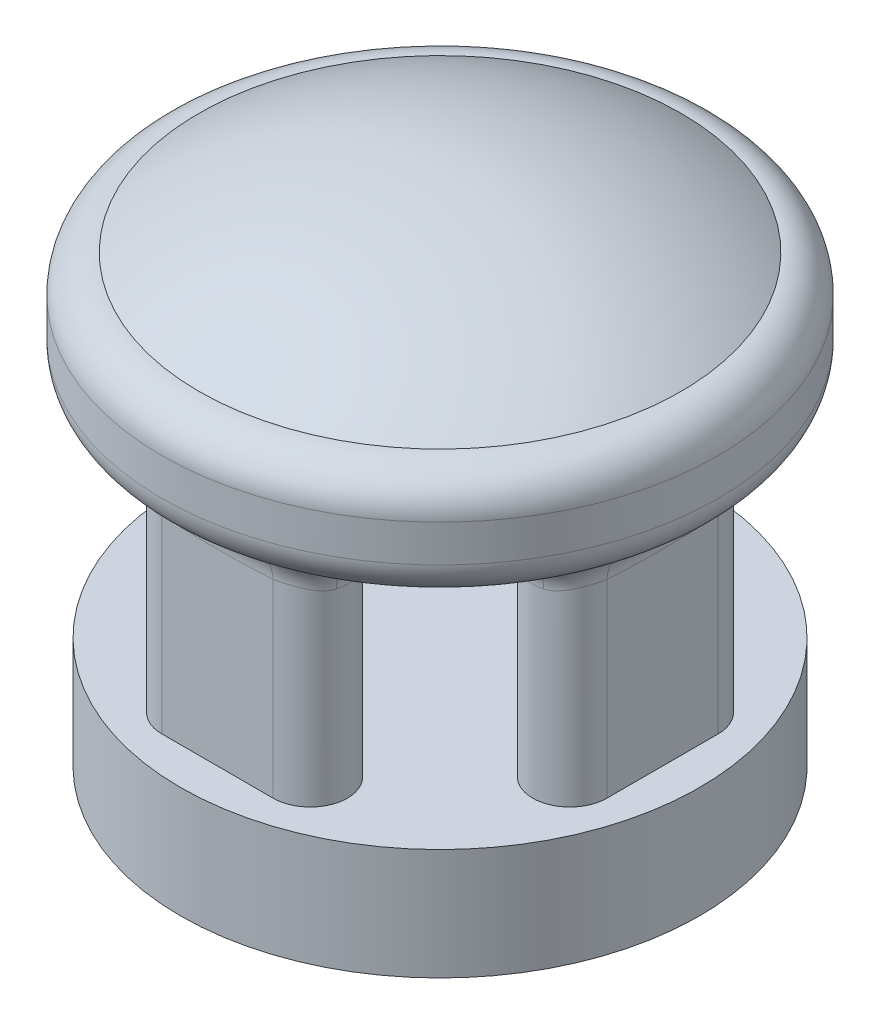
SolidWorks part; units mm, degrees
ref_plane "Front Plane" through (0, 0, 0) normal (0, 0, 1) x (1, 0, 0)
ref_plane "Top Plane" through (0, 0, 0) normal (0, 1, 0) x (1, 0, 0)
ref_plane "Right Plane" through (0, 0, 0) normal (1, 0, 0) x (0, 0, -1)
sketch "Sketch1" plane through (0, 0, 0) normal (0, 1, 0) x (1, 0, 0)
  circle A0 centre (0, 0) radius 9.525
  dimension "D1" = 19.05
extrude "button top" add sketch "Sketch1" along normal blind 3.81
sketch "Sketch2" plane through (0, 0, 0) normal (0, -1, 0) x (1, 0, 0)
  line L9 (-1.905, 6.35) -> (1.905, 6.35) construction
  line L10 (-1.905, 7.62) -> (1.905, 7.62)
  line L11 (-1.905, 5.08) -> (1.905, 5.08)
  arc A6 (-1.905, 7.62) -> (-1.905, 5.08) centre (-1.905, 6.35) ccw
  arc A7 (1.905, 5.08) -> (1.905, 7.62) centre (1.905, 6.35) ccw
  point P22 (0, 6.35)
  dimension "D2" = 1.27
  dimension "D1" = 6.35
  dimension "D8" = 3.81
extrude "connecting leg" add sketch "Sketch2" along normal blind 7.62
ref_axis "central axis" through (0, 3.81, 0) along (0, -1, 0)
pattern_circular "moar legs" count 4 over 360 about axis through (0, 3.81, 0) along (0, -1, 0) of "connecting leg"
ref_plane "base plane" through (0, -7.62, 0) normal (0, -1, 0) x (-1, 0, 0)
sketch "Sketch3" plane through (0, -7.62, 0) normal (0, -1, 0) x (-1, 0, 0)
  circle A0 centre (0, 0) radius 8.89
extrude "base" add sketch "Sketch3" along normal blind 3.81 separate body
fillet "Fillet2" radius 1.27 2 edges at (0, 3.81, 9.525) (0, 0, 9.525)
fillet "Fillet3" radius 1.27 16 edges at (0, 0, 5.08) (-3.175, 0, 6.35) (0, 0, 7.62) (3.175, 0, 6.35) (5.08, 0, 0) (6.35, 0, 3.175) (7.62, 0, 0) (6.35, 0, -3.175) (3.175, 0, -6.35) (0, 0, -7.62) (-3.175, 0, -6.35) (0, 0, -5.08) (-5.08, 0, 0) (-6.35, 0, -3.175) (-7.62, 0, 0) (-6.35, 0, 3.175)
dome "Dome1" faces to dome 1 distance 2.54 reverse direction no elliptical dome no face at (0, 3.81, 8.255) parameters "D1"=2.54
